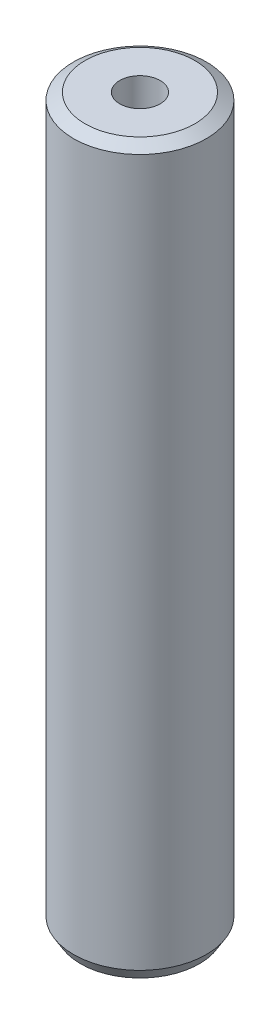
SolidWorks part; units mm, degrees
ref_plane "Front Plane" through (0, 0, 0) normal (0, 0, 1) x (1, 0, 0)
ref_plane "Top Plane" through (0, 0, 0) normal (0, 1, 0) x (1, 0, 0)
ref_plane "Right Plane" through (0, 0, 0) normal (1, 0, 0) x (0, 0, -1)
sketch "Sketch1" plane through (0, 0, 0) normal (0, 1, 0) x (1, 0, 0)
  circle A0 centre (0, 0) radius 55
  dimension "SHAFT_OD" = 110
extrude "Boss-Extrude1" add sketch "Sketch1" along normal blind 600
sketch "Sketch2" plane through (0, 0, 0) normal (0, 1, 0) x (1, 0, 0)
  circle A0 centre (0, 0) radius 16.7474
  dimension "BORE_D" = 33.4948
extrude "Cut-Extrude1" cut sketch "Sketch2" along normal through all
chamfer "Chamfer1" distance 5.809 angle 58.808 2 edges at (0, 600, 55) (0, 0, 55) first distance on face at (0, 600, 55) first distance on face at (0, 0, 16.7474)
